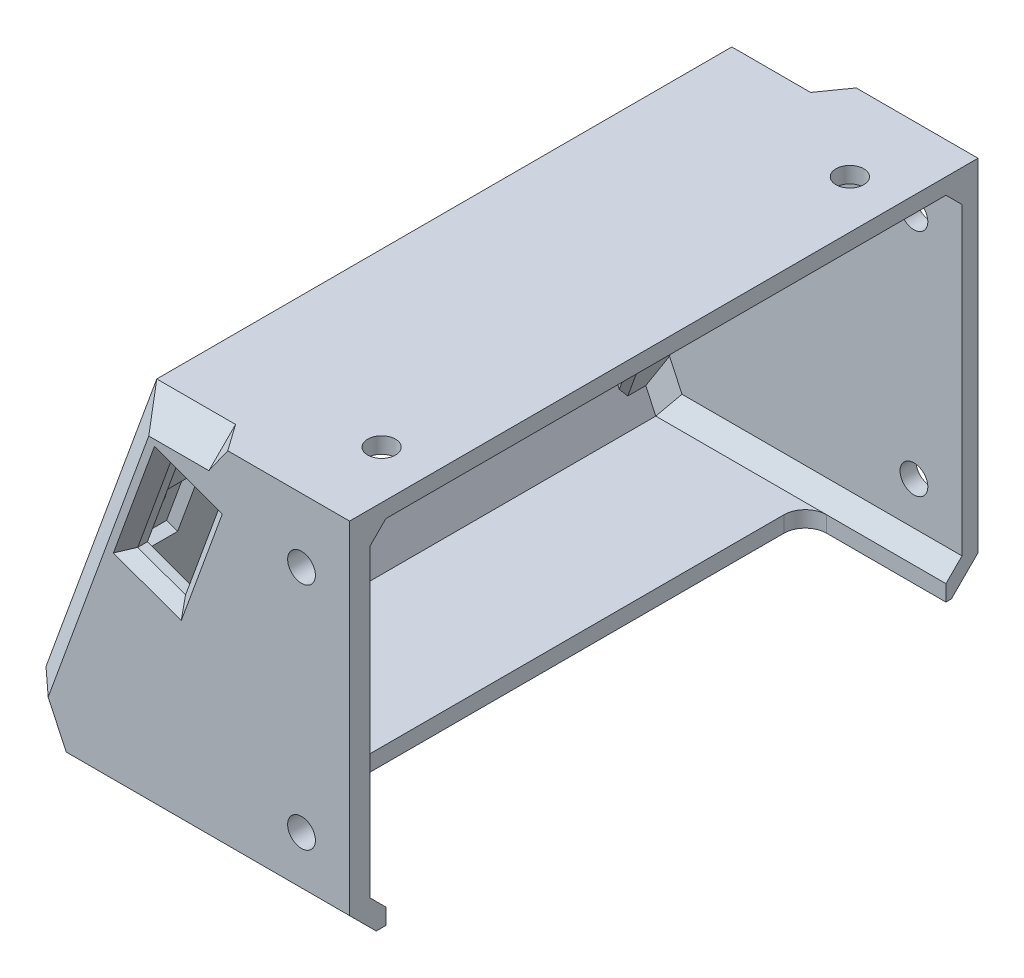
SolidWorks part; units mm, degrees
ref_plane "Front Plane" through (0, 0, 0) normal (0, 0, 1) x (1, 0, 0)
ref_plane "Top Plane" through (0, 0, 0) normal (0, 1, 0) x (1, 0, 0)
ref_plane "Right Plane" through (0, 0, 0) normal (1, 0, 0) x (0, 0, -1)
sketch "Sketch1" plane through (0, 0, 0) normal (0, 0, 1) x (1, 0, 0)
  line L0 (19, 70) -> (-15.7582, 70)
  line L1 (12.9286, 70) -> (-12.9286, 70) construction
  line L2 (-15.7582, 70) -> (-40.8722, 1)
  line L3 (-40.8722, 1) -> (20, 1)
  line L4 (20, 70) -> (20, 0) construction
  line L5 (19, 70) -> (19, 1)
  line L7 (-27.9872, 14.4727) -> (-10.2808, 63.1206) construction
  line L8 (10, 70) -> (10, 1) construction
  line L9 (0, 0) -> (0, 70) construction
  circle A0 centre (10, 58) radius 2.6
  circle A1 centre (10, 15) radius 2.6
  dimension "D1" = 1
  dimension "D4" = 12
  dimension "D5" = 14
  dimension "D6" = 5.2
  dimension "D2" = 69
  dimension "D3" = 7.5
  dimension "D7" = 10
extrude "Boss-Extrude1" add sketch "Sketch1" against normal blind 3.8 contours L0 L8 A0 A1 L3 L5 | L8 L0 L2 L3 A1 A0 region at (14.6203, 35.4646, 0) region at (-9.9952, 31.6925, 0)
ref_plane "Plane1" through (0, 0, -114.7) normal (0, 0, -1) x (-1, 0, 0)
sketch "Sketch2" plane through (0, 0, -114.7) normal (0, 0, -1) x (-1, 0, 0)
  line L0 (40.8722, 1) -> (-19, 1) construction
  line L1 (-19, 70) -> (-19, 1) construction
  line L2 (-19, 70) -> (15.7582, 70) construction
  line L3 (15.7582, 70) -> (40.8722, 1) construction
  line L4 (40.8722, 1) -> (-19, 1)
  line L5 (-19, 70) -> (-19, 1)
  line L6 (-19, 70) -> (15.7582, 70)
  line L7 (15.7582, 70) -> (40.8722, 1)
extrude "Boss-Extrude2" add sketch "Sketch2" along normal blind 3 separate body
sketch "Sketch3" plane through (0, 0, -3.8) normal (0, 0, -1) x (-1, 0, 0)
  line L0 (40.8722, 1) -> (-19, 1) construction
  line L1 (15.7582, 70) -> (40.8722, 1) construction
  line L2 (-19, 70) -> (15.7582, 70) construction
  line L3 (40.8722, 1) -> (-19, 1)
  line L4 (15.7582, 70) -> (40.8722, 1)
  line L5 (-19, 70) -> (15.7582, 70)
  line L6 (-19, 67) -> (13.6576, 67)
  line L7 (13.6576, 67) -> (36.5877, 4)
  line L8 (36.5877, 4) -> (-19, 4)
  line L9 (-19, 70) -> (-19, 67)
  line L10 (-19, 4) -> (-19, 1)
  dimension "D1" = 3
extrude "Boss-Extrude3" add sketch "Sketch3" along normal up to surface (110.9 mm away) up to face at (-4.6576, 35.5, -114.7)
sketch "Sketch4" plane through (-36.4124, 13.253, 0) normal (-0.9397, 0.342, 0) x (0, 0, 1)
  line L0 (-65.95, 55.7977) -> (-65.95, 4.0277) construction
  line L1 (-106.2, 55.7977) -> (-25.7, 55.7977)
  line L2 (-106.2, 55.7977) -> (-106.2, 4.0277)
  line L3 (-106.2, 4.0277) -> (-25.7, 4.0277)
  line L4 (-25.7, 55.7977) -> (-25.7, 4.0277)
  line L5 (-106.2, 29.9127) -> (-25.7, 29.9127) construction
  line L6 (-65.95, 28.7837) -> (-65.95, 30.2137) construction
  line L7 (-7.2097, 29.9127) -> (-5.7797, 29.9127) construction
  line L8 (-24.7, 56.7977) -> (-107.2, 56.7977) construction
  line L9 (-107.2, 56.7977) -> (-107.2, 3.0277) construction
  line L10 (-29.7, 55.7977) -> (-29.7, 4.0277)
  line L11 (-105.2, 55.7977) -> (-105.2, 4.0277)
  circle A0 centre (-13.8, 8.7277) radius 2
  circle A1 centre (-12.65, 28.6777) radius 4
  dimension "D1" = 1
  dimension "D3" = 8
  dimension "D4" = 4
  dimension "D2" = 1
  dimension "D5" = 4
  dimension "D6" = 1
extrude "Cut-Extrude1" cut sketch "Sketch4" against normal up to surface (3 mm away) contours L1 L11 L3 L10 | A1 | A0 region at (-26.1817, 41.3618, -67.45) region at (-33.4274, 21.4544, -13.8) region at (-26.6041, 40.2013, -12.65) up to face at (-25.1227, 35.5, -59.25)
sketch "Sketch5" plane through (0, 0, 0) normal (0, 0, 1) x (1, 0, 0)
  line L0 (-36.5045, 13) -> (-30.9088, 1)
  line L1 (-15.7582, 70) -> (-40.8722, 1) construction
  line L2 (-40.8722, 1) -> (19, 1) construction
  line L3 (-30.9088, 1) -> (-40.8722, 1)
  line L4 (-40.8722, 1) -> (-36.5045, 13)
  dimension "D1" = 135
  dimension "D2" = 12
extrude "Cut-Extrude2" cut sketch "Sketch5" against normal through all
sketch "Sketch6" plane through (0, 0, -3.8) normal (0, 0, -1) x (-1, 0, 0)
  line L0 (34.7115, 9.1549) -> (32.3078, 4)
  line L1 (32.3078, 4) -> (28.9976, 4)
  line L3 (33.2604, 13.1416) -> (28.9976, 4)
  line L4 (34.7115, 9.1549) -> (33.2604, 13.1416)
  line L6 (31.9926, 10.4227) -> (29.5888, 5.2679) construction
  line L7 (13.6576, 67) -> (34.7115, 9.1549) construction
  line L8 (32.3078, 4) -> (-19, 4) construction
  dimension "D1" = 3
extrude "Boss-Extrude4" add sketch "Sketch6" along normal up to surface (110.9 mm away) up to face at (-8.5354, 30.231, -114.7)
sketch "Sketch7" plane through (0, 70, 0) normal (0, 1, 0) x (1, 0, 0)
  line L0 (0, 0) -> (0, 117.7) construction
  line L1 (-15.7582, 117.7) -> (19, 117.7) construction
  line L2 (10, 0) -> (10, 117.7) construction
  line L4 (19, 0) -> (-15.7582, 0) construction
  circle A0 centre (10, 102.7) radius 2.6
  circle A1 centre (10, 15) radius 2.6
  dimension "D2" = 5.2
  dimension "D3" = 15
  dimension "D4" = 15
  dimension "D1" = 10
extrude "Cut-Extrude3" cut sketch "Sketch7" against normal up to surface (3 mm away) up to face at (2.6712, 67, -59.25)
sketch "Sketch8" plane through (-33.5933, 12.227, 0) normal (0.9397, -0.342, 0) x (0, 0, -1)
  line L5 (6.15, 22.1777) -> (19.15, 22.1777)
  line L6 (6.15, 22.1777) -> (6.15, 35.1777)
  line L7 (6.15, 35.1777) -> (19.15, 35.1777)
  line L8 (19.15, 22.1777) -> (19.15, 35.1777)
  line L9 (6.15, 22.1777) -> (19.15, 35.1777) construction
  line L10 (6.15, 35.1777) -> (19.15, 22.1777) construction
  point P2 (12.65, 28.6777)
  dimension "D1" = 13
  dimension "D2" = 13
extrude "Cut-Extrude4" cut sketch "Sketch8" against normal blind 2.2
sketch "Sketch9" plane through (-33.5933, 12.227, 0) normal (0.9397, -0.342, 0) x (0, 0, -1)
  line L0 (11.07, 5.1977) -> (11.07, 0.9734)
  line L1 (114.7, 0.9734) -> (3.8, 0.9734) construction
  line L2 (11.07, 0.9734) -> (3.8, 0.9734)
  line L3 (3.8, 0.9734) -> (3.8, 8.9477)
  line L4 (7.32, 50.8777) -> (3.8, 50.8777)
  line L5 (3.8, 58.2882) -> (3.8, 0.9734) construction
  line L6 (11.07, 54.6277) -> (11.07, 58.2882)
  line L8 (7.32, 8.9477) -> (3.8, 8.9477)
  line L9 (114.7, 58.2882) -> (3.8, 58.2882) construction
  line L10 (11.07, 58.2882) -> (3.8, 58.2882)
  line L11 (3.8, 58.2882) -> (3.8, 50.8777)
  line L12 (107.33, 54.6277) -> (107.33, 58.2882)
  line L13 (107.33, 58.2882) -> (114.7, 58.2882)
  line L14 (114.7, 58.2882) -> (114.7, 50.8777)
  line L15 (114.7, 0.9734) -> (114.7, 58.2882) construction
  line L16 (111.08, 50.8777) -> (114.7, 50.8777)
  line L17 (111.08, 8.9477) -> (114.7, 8.9477)
  line L18 (114.7, 8.9477) -> (114.7, 0.9734)
  line L19 (114.7, 0.9734) -> (107.33, 0.9734)
  line L20 (107.33, 0.9734) -> (107.33, 5.1977)
  circle A0 centre (7.32, 54.6277) radius 1.425
  circle A1 centre (111.08, 54.6277) radius 1.425
  circle A2 centre (7.32, 5.1977) radius 1.425
  circle A3 centre (111.08, 5.1977) radius 1.425
  arc A4 (7.32, 50.8777) -> (11.07, 54.6277) centre (7.32, 54.6277) ccw
  arc A6 (111.08, 8.9477) -> (107.33, 5.1977) centre (111.08, 5.1977) ccw
  arc A7 (11.07, 5.1977) -> (7.32, 8.9477) centre (7.32, 5.1977) ccw
  arc A8 (107.33, 54.6277) -> (111.08, 50.8777) centre (111.08, 54.6277) ccw
  dimension "D1" = 2.85
  dimension "D2" = 7.5
extrude "Boss-Extrude5" add sketch "Sketch9" along normal blind 4
sketch "Sketch10" plane through (19.9357, 54.773, 0) normal (0.342, 0.9397, 0) x (0.9397, -0.342, 0)
  line L0 (-35.7493, 114.7) -> (-35.7493, 107.33) construction
  line L1 (-35.7493, 107.33) -> (-31.7493, 107.33) construction
  line L2 (-31.7493, 107.33) -> (-31.7493, 114.7) construction
  line L3 (-31.7493, 114.7) -> (-35.7493, 114.7) construction
  line L4 (-35.7493, 11.07) -> (-35.7493, 3.8) construction
  line L5 (-35.7493, 3.8) -> (-31.7493, 3.8) construction
  line L6 (-31.7493, 3.8) -> (-31.7493, 11.07) construction
  line L7 (-31.7493, 11.07) -> (-35.7493, 11.07) construction
  line L8 (-35.7493, 114.7) -> (-35.7493, 107.33)
  line L9 (-35.7493, 107.33) -> (-31.7493, 107.33)
  line L10 (-31.7493, 107.33) -> (-31.7493, 114.7)
  line L11 (-31.7493, 114.7) -> (-35.7493, 114.7)
  line L12 (-35.7493, 11.07) -> (-35.7493, 3.8)
  line L13 (-35.7493, 3.8) -> (-31.7493, 3.8)
  line L14 (-31.7493, 3.8) -> (-31.7493, 11.07)
  line L15 (-31.7493, 11.07) -> (-35.7493, 11.07)
extrude "Boss-Extrude6" add sketch "Sketch10" along normal up to next
sketch "Sketch11" plane through (0.3329, 0.9147, 0) normal (-0.342, -0.9397, 0) x (0.9397, -0.342, 0)
  line L0 (-35.7493, -3.8) -> (-35.7493, -11.07) construction
  line L1 (-35.7493, -11.07) -> (-31.7493, -11.07) construction
  line L2 (-31.7493, -11.07) -> (-31.7493, -3.8) construction
  line L3 (-31.7493, -3.8) -> (-35.7493, -3.8) construction
  line L4 (-35.7493, -107.33) -> (-35.7493, -114.7) construction
  line L5 (-35.7493, -114.7) -> (-31.7493, -114.7) construction
  line L6 (-31.7493, -114.7) -> (-31.7493, -107.33) construction
  line L7 (-31.7493, -107.33) -> (-35.7493, -107.33) construction
  line L8 (-35.7493, -3.8) -> (-35.7493, -11.07)
  line L9 (-35.7493, -11.07) -> (-31.7493, -11.07)
  line L10 (-31.7493, -11.07) -> (-31.7493, -3.8)
  line L11 (-31.7493, -3.8) -> (-35.7493, -3.8)
  line L12 (-35.7493, -107.33) -> (-35.7493, -114.7)
  line L13 (-35.7493, -114.7) -> (-31.7493, -114.7)
  line L14 (-31.7493, -114.7) -> (-31.7493, -107.33)
  line L15 (-31.7493, -107.33) -> (-35.7493, -107.33)
extrude "Boss-Extrude7" add sketch "Sketch11" along normal up to next
chamfer "Chamfer8" distance 1 angle 45 12 edges at (-26.7743, 19.267, -112.89) (-29.4633, 11.879, -107.33) (-27.1499, 18.2349, -108.4283) (-29.4633, 11.879, -11.07) (-26.7743, 19.267, -5.56) (-27.1499, 18.2349, -9.9717) (-10.2758, 64.5961, -107.33) (-12.4334, 58.6683, -112.89) (-12.0577, 59.7004, -108.4283) (-12.4334, 58.6683, -5.56) (-10.2758, 64.5961, -11.07) (-12.0577, 59.7004, -9.9717)
sketch "Sketch12" plane through (-29.8346, 10.8589, 0) normal (0.9397, -0.342, 0) x (0, 0, -1)
  line L1 (16.975, 5.5527) -> (10.625, 5.5527)
  line L2 (16.975, 5.5527) -> (16.975, 11.9027)
  line L3 (16.975, 11.9027) -> (10.625, 11.9027)
  line L4 (10.625, 5.5527) -> (10.625, 11.9027)
  line L5 (16.975, 5.5527) -> (10.625, 11.9027) construction
  line L6 (16.975, 11.9027) -> (10.625, 5.5527) construction
  point P0 (13.8, 8.7277)
  dimension "D1" = 6.35
  dimension "D2" = 6.35
extrude "Cut-Extrude5" cut sketch "Sketch12" against normal up to surface (4 mm away) up to face at (-23.3867, 40.2695, -59.2125)
fillet "Fillet1" radius 1 2 edges at (-29.8001, 18.2632, -10.625) (-30.2847, 16.9318, -11.0532)
chamfer "Chamfer1" distance 2 angle 45 4 edges at (-35.0349, 17.0379, -67.45) (-17.3285, 65.6858, -67.45) (-26.1817, 41.3618, -29.7) (-26.1817, 41.3618, -105.2)
sketch "Sketch13" plane through (0, 0, -117.7) normal (0, 0, -1) x (-1, 0, 0)
  line L0 (8.9773, 50.621) -> (13.3938, 52.2285)
  line L1 (8.9773, 50.621) -> (18.4718, 24.5351)
  line L2 (13.3938, 52.2285) -> (22.8883, 26.1426)
  line L3 (18.4718, 24.5351) -> (22.8883, 26.1426)
  line L4 (8.7773, 62.5734) -> (12.7447, 51.6729) construction
  line L6 (21.7262, 26.9966) -> (12.8131, 51.485) construction
  line L7 (19.001, 26.0048) -> (10.088, 50.4932) construction
  line L8 (19.2574, 25.8852) -> (21.7946, 26.8087) construction
  line L9 (12.8131, 51.485) -> (10.2759, 50.5616) construction
  dimension "D1" = 0.5
  dimension "D2" = 0.8
  dimension "D3" = 1
  dimension "D4" = 1
extrude "Cut-Extrude6" cut sketch "Sketch13" against normal up to surface (3 mm away) up to face at (-14.3898, 35.2037, -114.7)
chamfer "Chamfer2" distance 1.2 angle 45 4 edges at (-20.6801, 25.3389, -117.7) (-13.7245, 37.578, -117.7) (-18.1411, 39.1855, -117.7) (-11.1856, 51.4247, -117.7)
chamfer "Chamfer3" distance 5 angle 45 8 edges at (1.6209, 70, -117.7) (-5.9544, 1, -117.7) (-33.7067, 7, -117.7) (-26.1314, 41.5, -117.7) (1.6209, 70, 0) (-5.9544, 1, 0) (-33.7067, 7, 0) (-26.1314, 41.5, 0)
chamfer "Chamfer4" distance 3 angle 45 8 edges at (-4.9988, 4, -3.8) (-29.9337, 6.0074, -3.8) (-23.3626, 40.3358, -3.8) (-23.3626, 40.3358, -114.7) (-29.9337, 6.0074, -114.7) (-4.9988, 4, -114.7) (4.7996, 67, -114.7) (4.7996, 67, -3.8)
sketch "Sketch14" plane through (0, 70, 0) normal (0, 1, 0) x (1, 0, 0)
  line L0 (-12.2572, 117.7) -> (19, 117.7) construction
  line L1 (19, 112.7) -> (3, 112.7)
  line L2 (19, 112.7) -> (19, 117.7)
  line L3 (19, 117.7) -> (3, 117.7)
  line L4 (3, 112.7) -> (3, 117.7)
  line L5 (-15.7582, 5) -> (19, 5) construction
  line L6 (19, 0) -> (3, 0)
  line L7 (19, 0) -> (19, 5)
  line L8 (19, 5) -> (3, 5)
  line L9 (3, 0) -> (3, 5)
  circle A0 centre (10, 102.7) radius 2.6 construction
  dimension "D1" = 7
extrude "Boss-Extrude8" add sketch "Sketch14" against normal up to next
chamfer "Chamfer5" distance 4 angle 45 2 edges at (3, 67.5, -115.2) (3, 67.5, -2.5)
sketch "Sketch15" plane through (0, 0, 0) normal (0, 0, 1) x (1, 0, 0)
  line L0 (-9.9891, 61.2905) -> (-1.0433, 58.0345)
  line L1 (-9.9891, 61.2905) -> (-16.3165, 43.9062)
  line L2 (-1.0433, 58.0345) -> (-7.3706, 40.6501)
  line L3 (-16.3165, 43.9062) -> (-7.3706, 40.6501)
  line L4 (-4, 55.7585) -> (-8.1726, 44.2942) construction
  line L5 (-9.1358, 57.7874) -> (-4.0897, 55.9507) construction
  line L6 (-13.3597, 46.1822) -> (-9.1358, 57.7874) construction
  line L7 (-8.3649, 44.2046) -> (-13.2701, 45.9899) construction
  dimension "D1" = 2
  dimension "D2" = 3
  dimension "D3" = 2
  dimension "D4" = 3
extrude "Cut-Extrude7" cut sketch "Sketch15" against normal up to surface (3.8 mm away) up to face at (12.6, 58, -3.8)
chamfer "Chamfer6" distance 2 angle 45 4 edges at (-11.8436, 42.2782, 0) (-13.1528, 52.5983, 0) (-5.5162, 59.6625, 0) (-4.2069, 49.3423, 0)
sketch "Sketch16" plane through (-33.5933, 12.227, 0) normal (0.9397, -0.342, 0) x (0, 0, -1)
  circle A0 centre (12.87, 44.6177) radius 5
  dimension "D1" = 10
extrude "Cut-Extrude8" cut sketch "Sketch16" against normal blind 1
sketch "Sketch17" plane through (-33.5933, 12.227, 0) normal (0.9397, -0.342, 0) x (0, 0, -1)
  line L0 (7.87, 44.6177) -> (17.87, 44.6177) construction
  line L1 (7.87, 45.6177) -> (17.87, 45.6177)
  line L2 (7.87, 43.6177) -> (17.87, 43.6177)
  line L3 (10.37, 48.1177) -> (15.37, 48.1177) construction
  line L4 (10.37, 49.1177) -> (15.37, 49.1177)
  line L5 (10.37, 47.1177) -> (15.37, 47.1177)
  line L6 (17.87, 44.6177) -> (22.8643, 44.6177) construction
  line L7 (10.37, 41.1177) -> (15.37, 41.1177) construction
  line L8 (10.37, 40.1177) -> (15.37, 40.1177)
  line L9 (10.37, 42.1177) -> (15.37, 42.1177)
  arc A0 (7.87, 45.6177) -> (7.87, 43.6177) centre (7.87, 44.6177) ccw
  arc A1 (17.87, 43.6177) -> (17.87, 45.6177) centre (17.87, 44.6177) ccw
  arc A2 (10.37, 49.1177) -> (10.37, 47.1177) centre (10.37, 48.1177) ccw
  arc A3 (15.37, 47.1177) -> (15.37, 49.1177) centre (15.37, 48.1177) ccw
  arc A4 (10.37, 40.1177) -> (10.37, 42.1177) centre (10.37, 41.1177) cw
  arc A5 (15.37, 42.1177) -> (15.37, 40.1177) centre (15.37, 41.1177) cw
  point P2 (12.87, 44.6177)
  point P10 (12.87, 48.1177)
  point P19 (12.87, 41.1177)
  dimension "D2" = 1
  dimension "D4" = 1
  dimension "D1" = 10
  dimension "D3" = 3.5
  dimension "D5" = 5
extrude "Cut-Extrude9" cut sketch "Sketch17" against normal through all
sketch "Sketch18" plane through (0, 0, -114.7) normal (0, 0, 1) x (1, 0, 0)
  circle A0 centre (10, 15) radius 2.6 construction
  circle A1 centre (10, 15) radius 2.6
extrude "Cut-Extrude10" cut sketch "Sketch18" against normal through all
sketch "Sketch19" plane through (-33.5933, 12.227, 0) normal (0.9397, -0.342, 0) x (0, 0, -1)
  circle A0 centre (111.08, 5.1977) radius 1.425 construction
  circle A1 centre (7.32, 5.1977) radius 1.425 construction
  circle A2 centre (111.08, 54.6277) radius 1.425 construction
  circle A3 centre (7.32, 54.6277) radius 1.425 construction
  circle A4 centre (111.08, 5.1977) radius 1.425
  circle A5 centre (7.32, 5.1977) radius 1.425
  circle A6 centre (111.08, 54.6277) radius 1.425
  circle A7 centre (7.32, 54.6277) radius 1.425
extrude "Cut-Extrude11" cut sketch "Sketch19" against normal blind 1.5
sketch "Sketch21" plane through (0, 4, 0) normal (0, 1, 0) x (1, 0, 0)
  line L0 (-28.9976, 6.8) -> (19, 6.8) construction
  line L1 (19, 111.7) -> (-1, 111.7)
  line L2 (19, 111.7) -> (19, 6.8)
  line L3 (19, 6.8) -> (-1, 6.8)
  line L4 (-1, 111.7) -> (-1, 6.8)
  dimension "D1" = 20
extrude "Cut-Extrude12" cut sketch "Sketch21" against normal up to surface (3 mm away) up to face at (-5.9544, 1, -58.85)
fillet "Fillet2" radius 4 2 edges at (-1, 2.5, -6.8) (-1, 2.5, -111.7)
sketch "Sketch22" plane through (19, 0, 0) normal (1, 0, 0) x (0, 0, -1)
  line L16 (114.7, 7) -> (111.7, 4)
  line L17 (111.7, 4) -> (111.7, 1)
  line L18 (111.7, 1) -> (112.7, 1)
  line L19 (112.7, 1) -> (117.7, 6)
  line L20 (117.7, 6) -> (117.7, 70)
  line L21 (117.7, 70) -> (0, 70)
  line L22 (0, 70) -> (0, 6)
  line L23 (0, 6) -> (5, 1)
  line L24 (5, 1) -> (6.8, 1)
  line L25 (6.8, 1) -> (6.8, 4)
  line L26 (6.8, 4) -> (3.8, 7)
  line L27 (3.8, 7) -> (3.8, 64)
  line L28 (3.8, 64) -> (6.8, 67)
  line L29 (6.8, 67) -> (111.7, 67)
  line L30 (111.7, 67) -> (114.7, 64)
  line L31 (114.7, 64) -> (114.7, 7)
  line L32 (114.7, 7) -> (111.7, 4)
  line L33 (111.7, 4) -> (111.7, 1)
  line L34 (111.7, 1) -> (112.7, 1)
  line L35 (112.7, 1) -> (117.7, 6)
  line L36 (117.7, 6) -> (117.7, 70)
  line L37 (117.7, 70) -> (0, 70)
  line L38 (0, 70) -> (0, 6)
  line L39 (0, 6) -> (5, 1)
  line L40 (5, 1) -> (6.8, 1)
  line L41 (6.8, 1) -> (6.8, 4)
  line L42 (6.8, 4) -> (3.8, 7)
  line L43 (3.8, 7) -> (3.8, 64)
  line L44 (3.8, 64) -> (6.8, 67)
  line L45 (6.8, 67) -> (111.7, 67)
  line L46 (111.7, 67) -> (114.7, 64)
  line L47 (114.7, 64) -> (114.7, 7)
  dimension "D1" = 0
extrude "Boss-Extrude9" add sketch "Sketch22" along normal blind 6.35
sketch "Sketch23" plane through (0, 0, 0) normal (0, 0, 1) x (1, 0, 0)
  circle A0 centre (10, 15) radius 2.6 construction
  circle A1 centre (10, 58) radius 2.6 construction
  circle A2 centre (10, 15) radius 2.6
  circle A3 centre (10, 58) radius 2.6
  circle A4 centre (16.35, 58) radius 2.6
  circle A5 centre (16.35, 15) radius 2.6
  dimension "D2" = 6.35
  dimension "D1" = 2
extrude "Boss-Extrude12" add sketch "Sketch23" against normal up to surface (3.8 mm away) contours A3 | A2 up to face at (-8.6799, 50.9703, -3.8)
extrude "Cut-Extrude13" cut sketch "Sketch23<3>" against normal through all contours A4 | A5
sketch "Sketch23<3>" plane through (0, 0, 0) normal (0, 0, 1) x (1, 0, 0) same geometry as "Sketch23"
sketch "Sketch24" plane through (0, 0, -117.7) normal (0, 0, -1) x (-1, 0, 0)
  circle A0 centre (-10, 15) radius 2.6 construction
  circle A1 centre (-10, 15) radius 2.6
extrude "Boss-Extrude13" add sketch "Sketch24" against normal up to surface (3 mm away) up to face at (16.35, 55.4, -114.7)
sketch "Sketch25" plane through (0, 70, 0) normal (0, 1, 0) x (1, 0, 0)
  circle A0 centre (10, 15) radius 2.6 construction
  circle A1 centre (10, 102.7) radius 2.6 construction
  circle A2 centre (10, 15) radius 2.6
  circle A3 centre (10, 102.7) radius 2.6
  circle A4 centre (16.35, 102.7) radius 2.6
  circle A5 centre (16.35, 15) radius 2.6
  dimension "D2" = 6.35
  dimension "D1" = 2
extrude "Boss-Extrude14" add sketch "Sketch25" against normal up to surface (3 mm away) contours A2 | A3 up to face at (10, 67, -100.1)
extrude "Cut-Extrude14" cut sketch "Sketch25<4>" against normal up to surface (3 mm away) contours A5 | A4 up to face at (-3.5149, 67, -59.22)
sketch "Sketch25<4>" plane through (0, 70, 0) normal (0, 1, 0) x (1, 0, 0) same geometry as "Sketch25"
equation "\"D2@Sketch15\"=\"D1@Sketch15\"+1"
equation "\"D3@Sketch15\"=\"D1@Sketch15\""
equation "\"D4@Sketch15\"=\"D1@Sketch15\"+1"
equation "\"D4@Sketch17\"=\"D2@Sketch17\""
